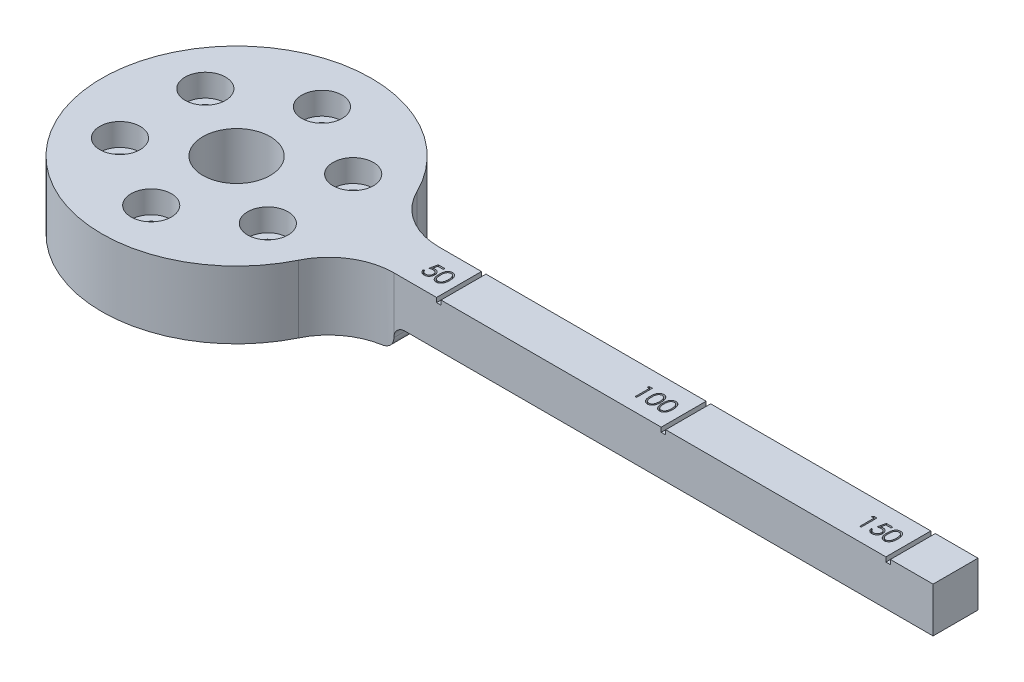
SolidWorks part; units mm, degrees
ref_plane "Front Plane" through (0, 0, 0) normal (0, 0, 1) x (1, 0, 0)
ref_plane "Top Plane" through (0, 0, 0) normal (0, 1, 0) x (1, 0, 0)
ref_plane "Right Plane" through (0, 0, 0) normal (1, 0, 0) x (0, 0, -1)
sketch "Sketch1" plane through (0, 0, 0) normal (0, 1, 0) x (1, 0, 0)
  line L2 (160, 5) -> (160, -5)
  line L3 (160, 5) -> (40, 5)
  line L4 (160, -5) -> (40, -5)
  arc A0 (26.9663, 13.1461) -> (26.9663, -13.1461) centre (0, 0) ccw
  circle A1 centre (0, 0) radius 7.5
  arc A2 (40, -5) -> (26.9663, -13.1461) centre (40, -19.5) ccw
  arc A3 (40, 5) -> (26.9663, 13.1461) centre (40, 19.5) cw
  point P7 (160, 0)
  dimension "D2" = 40
  dimension "D3" = 30
  dimension "D4" = 15
  dimension "D1" = 10
  dimension "D5" = 160
extrude "Boss-Extrude1" add sketch "Sketch1" along normal blind 15
sketch "Sketch2" plane through (0, 15, 0) normal (0, 1, 0) x (1, 0, 0)
  circle A0 centre (0, 0) radius 19 construction
  circle A1 centre (0, 19) radius 4.5
  circle A2 centre (16.4545, 9.5) radius 4.5
  circle A3 centre (16.4545, -9.5) radius 4.5
  circle A4 centre (0, -19) radius 4.5
  circle A5 centre (-16.4545, -9.5) radius 4.5
  circle A6 centre (-16.4545, 9.5) radius 4.5
  point P21 (0, 0)
  dimension "D1" = 38
  dimension "D2" = 9
  dimension "D3" = 6
extrude "Cut-Extrude1" cut sketch "Sketch2" against normal blind 5
sketch "Sketch3" plane through (0, 10, 0) normal (0, 1, 0) x (1, 0, 0)
  circle A0 centre (0, 19) radius 2.75
  circle A1 centre (16.4545, 9.5) radius 2.75
  circle A2 centre (16.4545, -9.5) radius 2.75
  circle A3 centre (0, -19) radius 2.75
  circle A4 centre (-16.4545, -9.5) radius 2.75
  circle A5 centre (-16.4545, 9.5) radius 2.75
  point P19 (0, 0)
  dimension "D1" = 5.5
  dimension "D2" = 6
extrude "Cut-Extrude2" cut sketch "Sketch3" against normal through all
sketch "Sketch4" plane through (0, 15, 0) normal (0, 1, 0) x (1, 0, 0)
  line L0 (49.5, 5) -> (49.5, -5)
  line L1 (160, 5) -> (40, 5) construction
  line L2 (40, -5) -> (160, -5) construction
  line L3 (50.5, 5) -> (50.5, -5)
  line L4 (99.5, 5) -> (99.5, -5)
  line L5 (100.5, 5) -> (100.5, -5)
  line L6 (149.5, 5) -> (149.5, -5)
  line L7 (150.5, 5) -> (150.5, -5)
  line L8 (49.5, 5) -> (50.5, 5)
  line L9 (49.5, -5) -> (50.5, -5)
  line L10 (99.5, 5) -> (100.5, 5)
  line L11 (99.5, -5) -> (100.5, -5)
  line L12 (149.5, 5) -> (150.5, 5)
  line L13 (149.5, -5) -> (150.5, -5)
  dimension "D1" = 1
  dimension "D2" = 49.5
  dimension "D3" = 1
  dimension "D4" = 99.5
  dimension "D5" = 1
  dimension "D6" = 149.5
extrude "Cut-Extrude3" cut sketch "Sketch4" against normal blind 1
sketch "Sketch5" plane through (0, 15, 0) normal (0, 1, 0) x (1, 0, 0)
  line L0 (49.5, 5) -> (49.5, -5) construction
  line L1 (99.5, 5) -> (99.5, -5) construction
  line L2 (149.5, 5) -> (149.5, -5) construction
  line L3 (49.5, 5) -> (40, 5) construction
  text T0 "50"
  text T1 "100"
  text T2 "150"
  dimension "D1" = 7
  dimension "D2" = 10
  dimension "D3" = 10
  dimension "D4" = 7
extrude "Cut-Extrude4" cut sketch "Sketch5" against normal blind 1
sketch "Sketch6" plane through (0, 0, 0) normal (0, 0, 1) x (1, 0, 0)
  line L0 (40, 15) -> (40, 0) construction
  line L1 (160, 0) -> (40, 0)
  line L2 (160, 0) -> (160, 5)
  line L3 (160, 5) -> (40, 5)
  line L4 (40, 0) -> (40, 5)
  dimension "D1" = 5
extrude "Cut-Extrude5" cut sketch "Sketch6" along normal mid plane 10
fillet "Fillet1" radius 2.5 2 edges at (40, 5, 0) (40, 0, 0)
